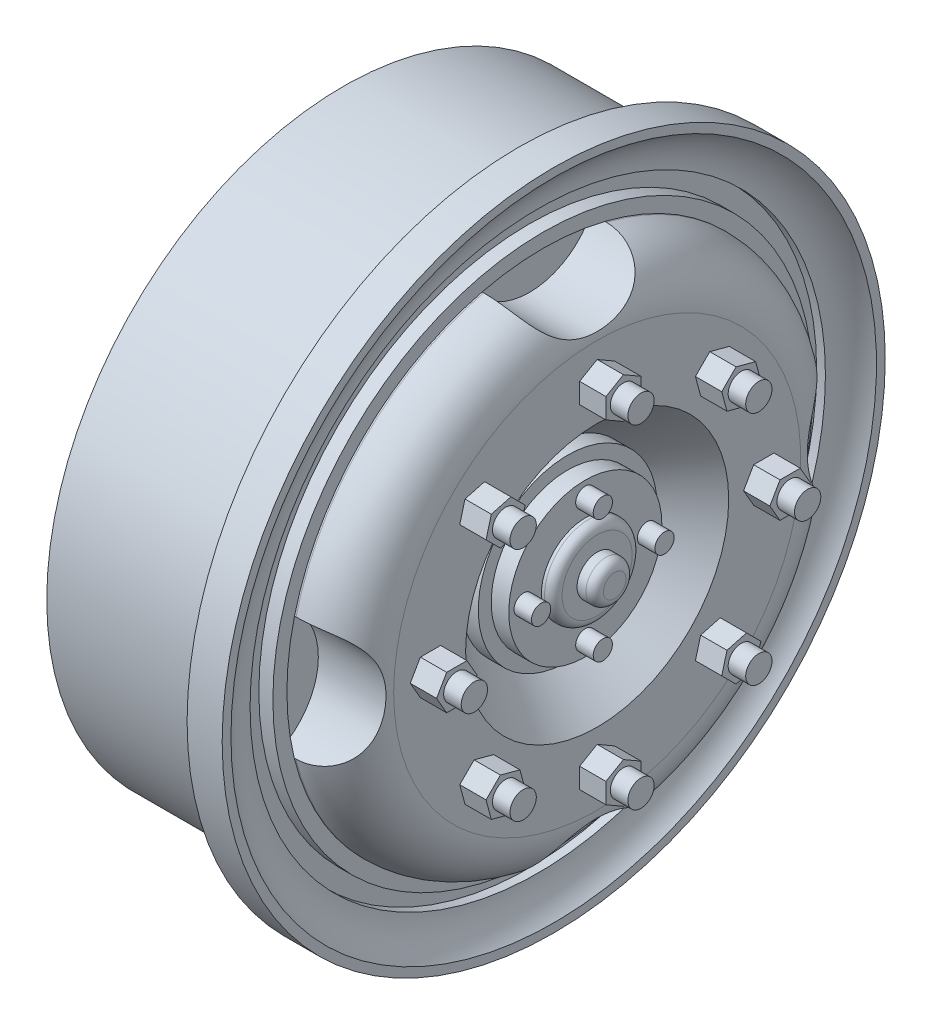
SolidWorks part; units mm, degrees
ref_plane "Front Plane" through (0, 0, 0) normal (0, 0, 1) x (1, 0, 0)
ref_plane "Top Plane" through (0, 0, 0) normal (0, 1, 0) x (1, 0, 0)
ref_plane "Right Plane" through (0, 0, 0) normal (1, 0, 0) x (0, 0, -1)
sketch "Sketch1" plane through (0, 0, 0) normal (0, 1, 0) x (1, 0, 0)
  line L0 (-25, 0) -> (25, 0) construction
  line L1 (0, 20.3358) -> (0, -18.8256) construction
  line L2 (-6, 16.9) -> (4, 16.9)
  line L3 (4, 16.9) -> (4, 18.9)
  line L4 (4, 18.9) -> (6, 18.9)
  line L5 (5.0904, 16.4) -> (4.5904, 16.4)
  line L6 (6, 18.9) -> (6, 18.4)
  line L7 (4.5904, 16.4) -> (4.5904, 15.4)
  line L8 (4.5904, 15.4) -> (5.3904, 15.4)
  line L9 (5.3904, 15.4) -> (5.3904, 14.6)
  line L20 (8.4765, 11.6) -> (8.4765, 7.5)
  line L25 (5.8, 5.1) -> (8.4765, 7.5)
  line L28 (-6, 10.5) -> (3.6177, 10.5)
  line L29 (3.6177, 10.5) -> (3.6177, 0)
  line L30 (5.8, 5.1) -> (5.8, 0)
  line L31 (5.8, 0) -> (3.6177, 0)
  line L32 (-6, 16.9) -> (-6, 10.5)
  line L33 (5.3904, 14.6) -> (5.4765, 14.6)
  arc A0 (6, 18.4) -> (5.0904, 16.4) centre (7.7439, 16.4) ccw
  arc A4 (8.4765, 11.6) -> (5.4765, 14.6) centre (5.4765, 11.6) ccw
  point P23 (8.5904, 13.6)
  point P24 (8.4765, 13.6)
  point P25 (8.4765, 13.9348)
  dimension "D15" = 3
  dimension "D1" = 50
  dimension "D2" = 25
  dimension "D3" = 37.8
  dimension "D4" = 2
  dimension "D5" = 2
  dimension "D6" = 10
  dimension "D7" = 6
  dimension "D8" = 0.5
  dimension "D9" = 0.5
  dimension "D10" = 2
  dimension "D11" = 1
  dimension "D12" = 0.8
  dimension "D13" = 0.8
  dimension "D14" = 1
  dimension "D18" = 15
  dimension "D20" = 21
revolve "Revolve1" add sketch "Sketch1" angle 360 about L0
sketch "Sketch2" plane through (5.8, 0, 0) normal (1, 0, 0) x (0, 0, -1)
  circle A0 centre (0, 0) radius 2.5
  dimension "D1" = 5
extrude "Boss-Extrude1" add sketch "Sketch2" along normal up to surface (2.6765 mm away) up to face at (8.4765, 0, 11.6)
fillet "Fillet2" radius 0.5 1 edges at (8.4765, 0, 2.5)
sketch "Sketch3" plane through (8.4765, 0, 0) normal (1, 0, 0) x (0, 0, -1)
  circle A0 centre (0, 0) radius 1.1449
extrude "Boss-Extrude4" add sketch "Sketch3" along normal blind 1
fillet "Fillet3" radius 0.5 1 edges at (9.4765, 0, -1.1449)
sketch "Sketch5" plane through (8.4765, 0, 0) normal (1, 0, 0) x (0, 0, -1)
  line L0 (5.901, 5.901) -> (7.0164, 5.6022)
  line L1 (0, 8.3453) -> (1, 8.9226)
  line L2 (1, 8.9226) -> (1, 10.0774)
  line L3 (1, 10.0774) -> (0, 10.6547)
  line L4 (0, 10.6547) -> (-1, 10.0774)
  line L5 (-1, 10.0774) -> (-1, 8.9226)
  line L6 (-1, 8.9226) -> (0, 8.3453)
  line L7 (7.0164, 5.6022) -> (7.8329, 6.4187)
  line L8 (7.8329, 6.4187) -> (7.534, 7.534)
  line L9 (7.534, 7.534) -> (6.4187, 7.8329)
  line L10 (6.4187, 7.8329) -> (5.6022, 7.0164)
  line L11 (5.6022, 7.0164) -> (5.901, 5.901)
  line L12 (8.3453, 0) -> (8.9226, -1)
  line L13 (8.9226, -1) -> (10.0774, -1)
  line L14 (10.0774, -1) -> (10.6547, 0)
  line L15 (10.6547, 0) -> (10.0774, 1)
  line L16 (10.0774, 1) -> (8.9226, 1)
  line L17 (8.9226, 1) -> (8.3453, 0)
  line L18 (5.901, -5.901) -> (5.6022, -7.0164)
  line L19 (5.6022, -7.0164) -> (6.4187, -7.8329)
  line L20 (6.4187, -7.8329) -> (7.534, -7.534)
  line L21 (7.534, -7.534) -> (7.8329, -6.4187)
  line L22 (7.8329, -6.4187) -> (7.0164, -5.6022)
  line L23 (7.0164, -5.6022) -> (5.901, -5.901)
  line L24 (0, -8.3453) -> (-1, -8.9226)
  line L25 (-1, -8.9226) -> (-1, -10.0774)
  line L26 (-1, -10.0774) -> (0, -10.6547)
  line L27 (0, -10.6547) -> (1, -10.0774)
  line L28 (1, -10.0774) -> (1, -8.9226)
  line L29 (1, -8.9226) -> (0, -8.3453)
  line L30 (-5.901, -5.901) -> (-7.0164, -5.6022)
  line L31 (-7.0164, -5.6022) -> (-7.8329, -6.4187)
  line L32 (-7.8329, -6.4187) -> (-7.534, -7.534)
  line L33 (-7.534, -7.534) -> (-6.4187, -7.8329)
  line L34 (-6.4187, -7.8329) -> (-5.6022, -7.0164)
  line L35 (-5.6022, -7.0164) -> (-5.901, -5.901)
  line L36 (-8.3453, 0) -> (-8.9226, 1)
  line L37 (-8.9226, 1) -> (-10.0774, 1)
  line L38 (-10.0774, 1) -> (-10.6547, 0)
  line L39 (-10.6547, 0) -> (-10.0774, -1)
  line L40 (-10.0774, -1) -> (-8.9226, -1)
  line L41 (-8.9226, -1) -> (-8.3453, 0)
  line L42 (-5.901, 5.901) -> (-5.6022, 7.0164)
  line L43 (-5.6022, 7.0164) -> (-6.4187, 7.8329)
  line L44 (-6.4187, 7.8329) -> (-7.534, 7.534)
  line L45 (-7.534, 7.534) -> (-7.8329, 6.4187)
  line L46 (-7.8329, 6.4187) -> (-7.0164, 5.6022)
  line L47 (-7.0164, 5.6022) -> (-5.901, 5.901)
  circle A0 centre (0, 0) radius 9.5 construction
  circle A1 centre (0, 9.5) radius 1 construction
  point P56 (0, 0)
  dimension "D2" = 19
  dimension "D3" = 2
  dimension "D1" = 8
extrude "Boss-Extrude2" add sketch "Sketch5" along normal blind 1.5
sketch "Sketch6" plane through (9.9765, 0, 0) normal (1, 0, 0) x (0, 0, -1)
  line L0 (0, -8.3453) -> (0, -10.6547) construction
  line L1 (-1, -8.9226) -> (1, -10.0774) construction
  circle A0 centre (0, -9.5) radius 0.75
  circle A14 centre (-6.7175, -6.7175) radius 0.75
  circle A15 centre (-9.5, 0) radius 0.75
  circle A16 centre (-6.7175, 6.7175) radius 0.75
  circle A17 centre (0, 9.5) radius 0.75
  circle A18 centre (6.7175, 6.7175) radius 0.75
  circle A19 centre (9.5, 0) radius 0.75
  circle A20 centre (6.7175, -6.7175) radius 0.75
  point P29 (-1.0447, 0.4327)
  point P42 (0, 0)
  dimension "D1" = 1.5
  dimension "D3" = 8
extrude "Boss-Extrude3" add sketch "Sketch6" along normal blind 1
sketch "Sketch7" plane through (5.8, 0, 0) normal (1, 0, 0) x (0, 0, -1)
  circle A1 centre (0, 0) radius 5.1
  circle A2 centre (0, 0) radius 5.1
  dimension "D1" = 0
extrude "Boss-Extrude5" add sketch "Sketch7" along normal blind 1
sketch "Sketch8" plane through (6.8, 0, 0) normal (1, 0, 0) x (0, 0, -1)
  circle A0 centre (0, 0) radius 4.3648
extrude "Boss-Extrude6" add sketch "Sketch8" along normal blind 1
sketch "Sketch9" plane through (7.8, 0, 0) normal (1, 0, 0) x (0, 0, -1)
  circle A0 centre (0, 0) radius 3.5178 construction
  circle A1 centre (0, 3.5178) radius 0.548
  circle A2 centre (3.5178, 0) radius 0.548
  circle A3 centre (0, -3.5178) radius 0.548
  circle A4 centre (-3.5178, 0) radius 0.548
  point P14 (0, 0)
  dimension "D1" = 4
extrude "Boss-Extrude7" add sketch "Sketch9" along normal blind 1
sketch "Sketch10" plane through (8.4765, 0, 0) normal (1, 0, 0) x (0, 0, -1)
  line L0 (0, 14.6) -> (0, -14.6) construction
  line L1 (-14.6, 0) -> (14.6, 0) construction
  arc A0 (14.181, 3.4725) -> (14.1675, -3.5275) centre (15.9176, -0.0309) ccw
  arc A2 (-3.4725, 14.181) -> (3.5275, 14.1675) centre (0.0309, 15.9176) ccw
  arc A3 (3.5275, 14.1675) -> (-3.4725, 14.181) centre (0, 0) ccw
  arc A4 (14.1675, -3.5275) -> (14.181, 3.4725) centre (0, 0) ccw
  arc A5 (3.4725, -14.181) -> (-3.5275, -14.1675) centre (-0.0309, -15.9176) ccw
  arc A6 (-3.5275, -14.1675) -> (3.4725, -14.181) centre (0, 0) ccw
  arc A7 (-14.181, -3.4725) -> (-14.1675, 3.5275) centre (-15.9176, 0.0309) ccw
  arc A8 (-14.1675, 3.5275) -> (-14.181, -3.4725) centre (0, 0) ccw
  point P20 (0, 0)
  dimension "D1" = 7
  dimension "D2" = 3.5275
  dimension "D3" = 4
extrude "Cut-Extrude1" cut sketch "Sketch10" against normal up to surface (3.8861 mm away) up to face at (4.5904, 0, 16.4)
